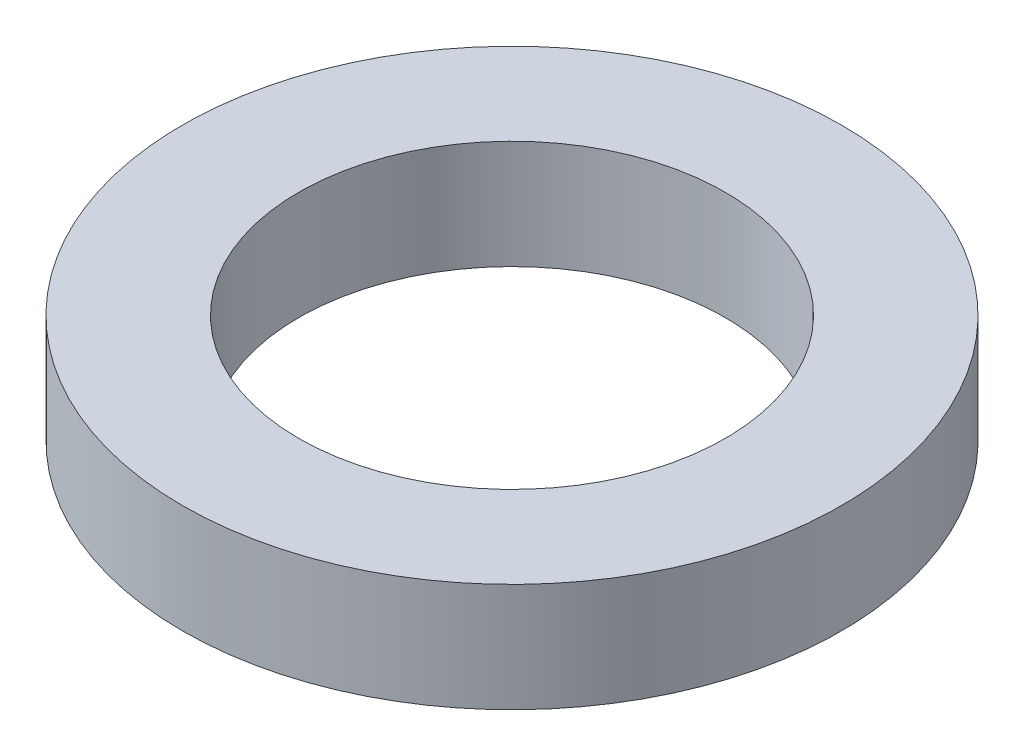
SolidWorks part; units mm, degrees
ref_plane "Front Plane" through (0, 0, 0) normal (0, 0, 1) x (1, 0, 0)
ref_plane "Top Plane" through (0, 0, 0) normal (0, 1, 0) x (1, 0, 0)
ref_plane "Right Plane" through (0, 0, 0) normal (1, 0, 0) x (0, 0, -1)
sketch "Sketch1" plane through (0, 0, 0) normal (0, 1, 0) x (1, 0, 0)
  circle A0 centre (0, 0) radius 42.5
  dimension "FLANGE_OD" = 85
extrude "Boss-Extrude1" add sketch "Sketch1" along normal blind 14
sketch "Sketch2" plane through (0, 0, 0) normal (0, 1, 0) x (1, 0, 0)
  circle A0 centre (0, 0) radius 27.5
  dimension "BORE_D" = 55
extrude "Cut-Extrude1" cut sketch "Sketch2" along normal through all
sketch "Sketch3" plane through (0, 14, 0) normal (0, 1, 0) x (1, 0, 0)
  circle A0 centre (0, 0) radius 16.2266 construction
  circle A1 centre (-16.2266, 0) radius 2.2226
  dimension "BOLT_D" = 4.4452
  dimension "BOLT_PCD" = 32.4532
extrude "Cut-Extrude2" cut sketch "Sketch3" against normal blind 10.4877 rebuild error yes
pattern_circular "CirPattern1" count 8 over 360 rebuild error yes
